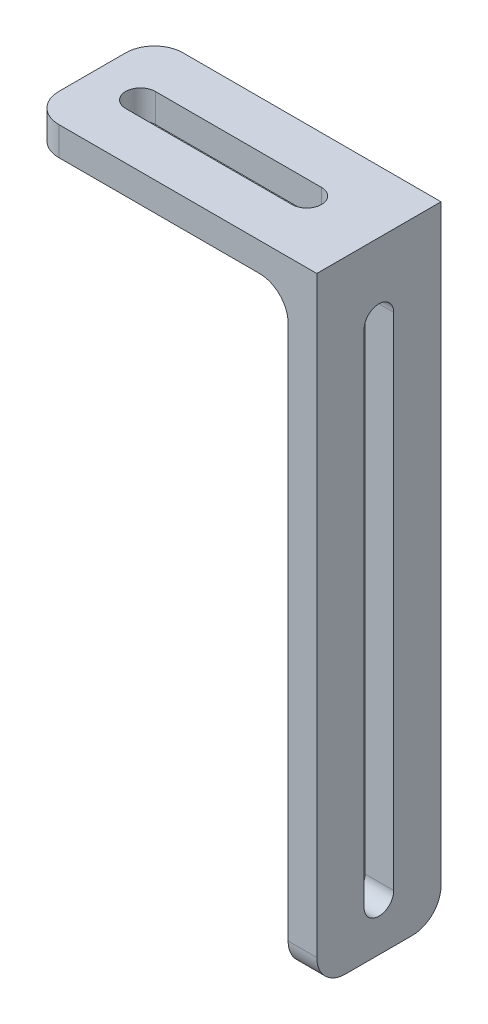
SolidWorks part; units mm, degrees
ref_plane "Front Plane" through (0, 0, 0) normal (0, 0, 1) x (1, 0, 0)
ref_plane "Top Plane" through (0, 0, 0) normal (0, 1, 0) x (1, 0, 0)
ref_plane "Right Plane" through (0, 0, 0) normal (1, 0, 0) x (0, 0, -1)
sketch "Sketch1" plane through (0, 0, 0) normal (0, 0, 1) x (1, 0, 0)
  line L0 (0, 0) -> (3, 0)
  line L1 (3, 0) -> (3, 65)
  line L2 (3, 65) -> (-27, 65)
  line L3 (-27, 65) -> (-27, 62)
  line L4 (-27, 62) -> (0, 62)
  line L5 (0, 62) -> (0, 0)
  dimension "D1" = 27
  dimension "D2" = 65
  dimension "D3" = 3
  dimension "D4" = 3
extrude "Boss-Extrude1" add sketch "Sketch1" along normal blind 13
sketch "Sketch6" plane through (3, 0, 0) normal (1, 0, 0) x (0, 0, -1)
  line L0 (-6.5, 65) -> (-6.5, 0) construction
  line L1 (-13, 65) -> (0, 65) construction
  line L2 (-13, 0) -> (0, 0) construction
  line L3 (-6.5, 57.45) -> (-6.5, 5.05) construction
  line L4 (-4.95, 57.45) -> (-4.95, 5.05)
  line L5 (-8.05, 57.45) -> (-8.05, 5.05)
  arc A0 (-4.95, 57.45) -> (-8.05, 57.45) centre (-6.5, 57.45) ccw
  arc A1 (-8.05, 5.05) -> (-4.95, 5.05) centre (-6.5, 5.05) ccw
  point P8 (-6.5, 31.25)
  point P13 (-6.5, 59)
  point P14 (-6.5, 3.5)
  dimension "D1" = 3.1
  dimension "D2" = 6
  dimension "D3" = 3.5
  dimension "D4" = 55.5
extrude "Cut-Extrude1" cut sketch "Sketch6" against normal through all
sketch "Sketch7" plane through (0, 65, 0) normal (0, 1, 0) x (1, 0, 0)
  line L0 (-27, -6.5) -> (3, -6.5) construction
  line L1 (-27, -13) -> (-27, 0) construction
  line L2 (3, -13) -> (3, 0) construction
  line L3 (-21.95, -6.5) -> (-4.55, -6.5) construction
  line L4 (-21.95, -4.95) -> (-4.55, -4.95)
  line L5 (-21.95, -8.05) -> (-4.55, -8.05)
  arc A0 (-21.95, -4.95) -> (-21.95, -8.05) centre (-21.95, -6.5) ccw
  arc A1 (-4.55, -8.05) -> (-4.55, -4.95) centre (-4.55, -6.5) ccw
  point P8 (-13.25, -6.5)
  point P13 (-23.5, -6.5)
  point P14 (-3, -6.5)
  dimension "D2" = 6
  dimension "D1" = 3.5
  dimension "D3" = 3.1
  dimension "D4" = 20.5
extrude "Cut-Extrude2" cut sketch "Sketch7" against normal through all contours L4 A1 L5 A0
fillet "Fillet1" radius 3 1 edges at (0, 62, 6.5)
fillet "Fillet2" radius 3 4 edges at (1.5, 0, 0) (1.5, 0, 13) (-27, 63.5, 13) (-27, 63.5, 0)
sketch "Sketch8" plane through (0, 65, 0) normal (0, 1, 0) x (1, 0, 0)
  line L0 (-23.5, -6.5) -> (-3, -6.5) construction
  arc A0 (-21.95, -4.95) -> (-21.95, -8.05) centre (-21.95, -6.5) ccw construction
sketch "Sketch9" plane through (3, 0, 0) normal (1, 0, 0) x (0, 0, -1)
  line L0 (-6.5, 59) -> (-6.5, 3.5) construction
  arc A0 (-8.05, 5.05) -> (-4.95, 5.05) centre (-6.5, 5.05) ccw construction
